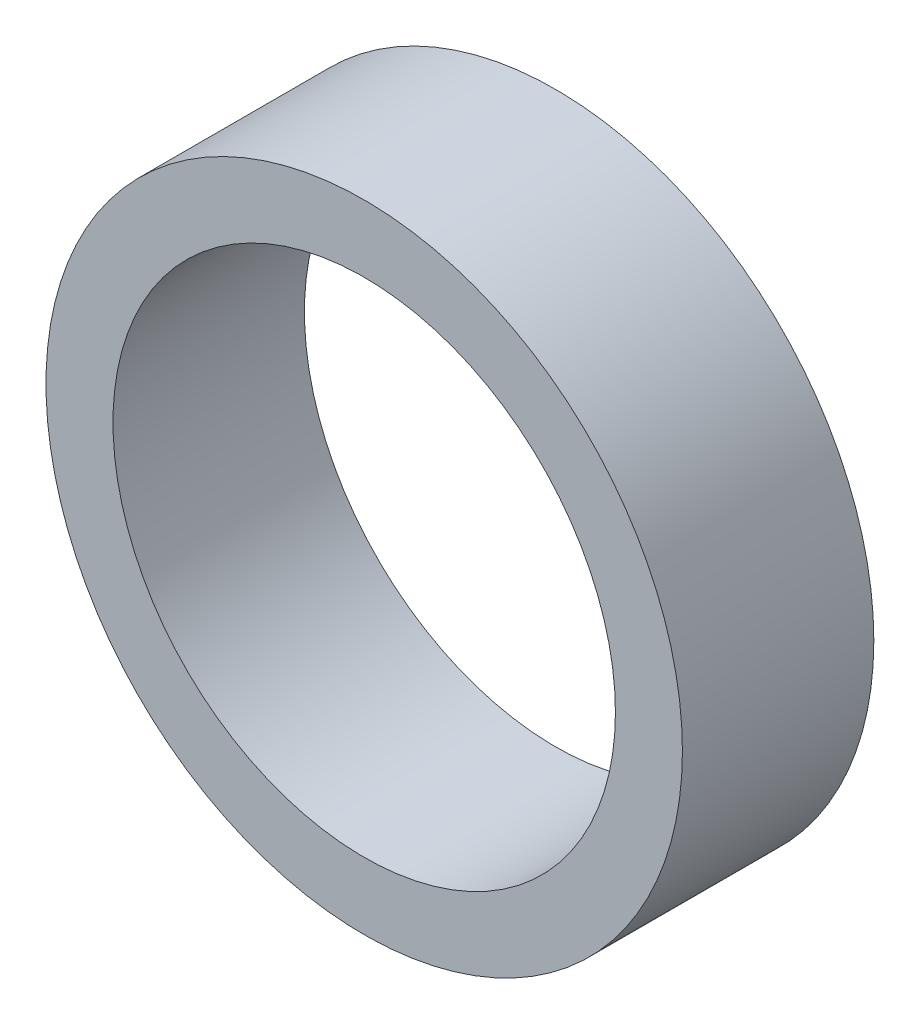
SolidWorks part; units mm, degrees
material "ABS"
ref_plane "Front Plane" through (0, 0, 0) normal (0, 0, 1) x (1, 0, 0)
ref_plane "Top Plane" through (0, 0, 0) normal (0, 1, 0) x (1, 0, 0)
ref_plane "Right Plane" through (0, 0, 0) normal (1, 0, 0) x (0, 0, -1)
sketch "Sketch1" plane through (0, 0, 3) normal (0, 0, 1) x (1, 0, 0)
  circle A0 centre (32.5, 0) radius 3.325
  circle A1 centre (32.5, 0) radius 2.625
  dimension "D1" = 6.65
  dimension "D2" = 5.25
extrude "Boss-Extrude1" add sketch "Sketch1" along normal blind 2 from offset 5
equation "\"RingPinShaft\"= 5.05"
equation "\"CenterBearingOut\"=32.00"
equation "\"OutputBearingOut\"=37.00"
equation "\"RingPostIn\"=5.15"
equation "\"CamBearingOut\"=15.1"
equation "\"DiskOutputShaft\"=10.1"
equation "\"CenterShaft\"=25.2"
equation "\"Eccentricity\"=2"
equation "\"CycCamShaft\"=10.05"
equation "\"m3Thru\"=3.15"
equation "\"m3Insert\"=4.2"
equation "\"D2@Sketch1\"=\"RingPostIn\"+0.1"
equation "\"D1@Sketch1\"=\"RingPostIn\"+1.5"
